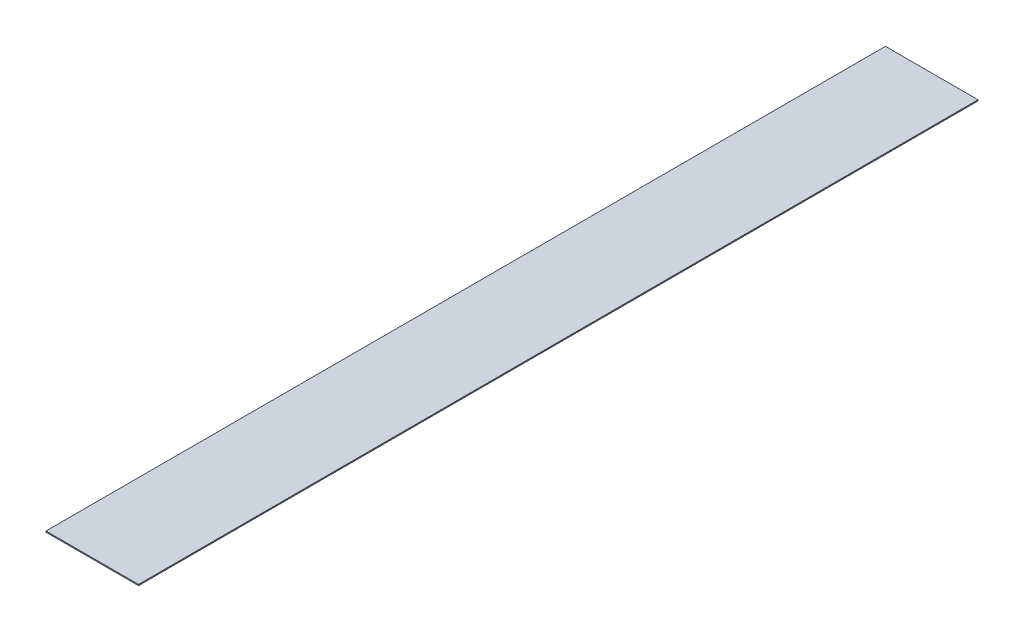
SolidWorks part; units mm, degrees
ref_plane "Front Plane" through (0, 0, 0) normal (0, 0, 1) x (1, 0, 0)
ref_plane "Top Plane" through (0, 0, 0) normal (0, 1, 0) x (1, 0, 0)
ref_plane "Right Plane" through (0, 0, 0) normal (1, 0, 0) x (0, 0, -1)
sketch "Sketch2" plane through (0, 0, 0) normal (0, 1, 0) x (1, 0, 0)
  line L0 (2.15, -19.5) -> (2.15, 19.5)
  line L1 (-2.15, -19.5) -> (-2.15, 19.5)
  line L2 (2.15, -19.5) -> (-2.15, -19.5)
  line L3 (2.15, 19.5) -> (-2.15, 19.5)
  line L4 (2.15, 19.5) -> (-2.15, -19.5) construction
  line L5 (-2.15, 19.5) -> (2.15, -19.5) construction
  point P2 (0, -19.5)
  point P5 (0, 19.5)
  point P6 (0, 0)
  dimension "D1" = 39
  dimension "D2" = 4.3
extrude "Boss-Extrude1" add sketch "Sketch2" along normal mid plane 0.05
